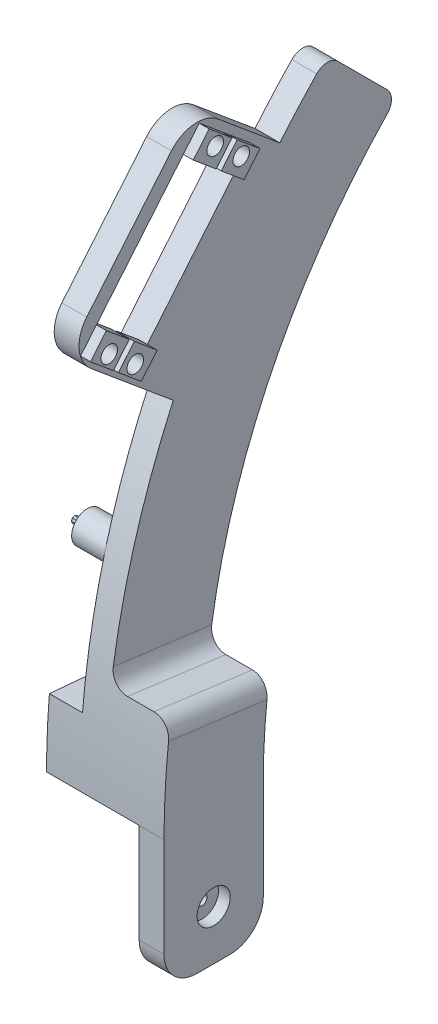
SolidWorks part; units mm, degrees
ref_plane "Front Plane" through (0, 0, 0) normal (0, 0, 1) x (1, 0, 0)
ref_plane "Top Plane" through (0, 0, 0) normal (0, 1, 0) x (1, 0, 0)
ref_plane "Right Plane" through (0, 0, 0) normal (1, 0, 0) x (0, 0, -1)
sketch "Sketch2" plane through (0, 0, 0) normal (1, 0, 0) x (0, 0, -1)
  line L0 (-197.177, 0) -> (-167.177, 0)
  line L1 (-129.8116, 162.6346) -> (-108.5984, 141.4214)
  arc A0 (-167.177, 0) -> (-108.5984, 141.4214) centre (32.823, 0) cw
  arc A1 (-197.177, 0) -> (-129.8116, 162.6346) centre (32.823, 0) cw
  dimension "D4" = 200
  dimension "D1" = 30
  dimension "D2" = 30
  dimension "D3" = 45
extrude "Curve Main Body" add sketch "Sketch2" along normal blind 35.5
sketch "Sketch6" plane through (35.5, 0, 0) normal (1, 0, 0) x (0, 0, -1)
  line L0 (-165.466, 26.1052) -> (-195.2093, 30.021)
  line L1 (-108.5984, 141.4214) -> (-129.8116, 162.6346)
  line L2 (-197.177, 0) -> (-167.177, 0) construction
  arc A0 (-108.5984, 141.4214) -> (-167.177, 0) centre (32.823, 0) ccw construction
  arc A1 (-129.8116, 162.6346) -> (-197.177, 0) centre (32.823, 0) ccw construction
  arc A2 (-165.466, 26.1052) -> (-108.5984, 141.4214) centre (32.823, 0) cw
  arc A3 (-129.8116, 162.6346) -> (-195.2093, 30.021) centre (32.823, 0) ccw
  dimension "D1" = 30
  dimension "D2" = 7.5
extrude "Cut-Extrude2" cut sketch "Sketch6" against normal offset from surface (18 mm away) 17.5 up to face at (0, 79.1455, 158.2511)
sketch "Sketch7" plane through (0, 0, 0) normal (-1, 0, 0) x (0, 0, 1)
  line L0 (166.416, 17.4311) -> (196.3018, 20.0458)
  line L1 (167.177, 0) -> (197.177, 0) construction
  line L3 (129.8116, 162.6346) -> (108.5984, 141.4214)
  arc A0 (167.177, 0) -> (108.5984, 141.4214) centre (-32.823, 0) ccw construction
  arc A1 (197.177, 0) -> (129.8116, 162.6346) centre (-32.823, 0) ccw construction
  arc A2 (196.3018, 20.0458) -> (129.8116, 162.6346) centre (-32.823, 0) ccw
  arc A3 (108.5984, 141.4214) -> (166.416, 17.4311) centre (-32.823, 0) cw
  dimension "D1" = 30
  dimension "D2" = 5
extrude "Cut-Extrude3" cut sketch "Sketch7" against normal offset from surface (10 mm away) 7.5 up to face at (17.5, 92.5688, 154.888)
fillet "Fillet3" radius 5 2 edges at (35.5, 28.0631, 180.3377) (17.5, 28.0631, 180.3377)
mirror "Mirror3" about plane through (0, 0, -32.823) normal (-1, 0, 0) of "Curve Main Body", "Cut-Extrude2", "Cut-Extrude3", "Fillet3"
sketch "Sketch14" plane through (0, 0, 0) normal (0, -1, 0) x (1, 0, 0)
  line L0 (35.5, 167.177) -> (-35.5, 167.177) construction
  line L1 (-35.5, 197.177) -> (-28, 197.177)
  line L2 (-35.5, 197.177) -> (-35.5, 167.177)
  line L3 (-35.5, 167.177) -> (-28, 167.177)
  line L4 (-28, 197.177) -> (-28, 167.177)
  line L5 (0, 197.177) -> (0, 167.177) construction
  line L6 (35.5, 197.177) -> (-35.5, 197.177) construction
  line L7 (28, 197.177) -> (28, 167.177)
  line L8 (35.5, 167.177) -> (28, 167.177)
  line L9 (35.5, 197.177) -> (35.5, 167.177)
  line L10 (35.5, 197.177) -> (28, 197.177)
  dimension "D1" = 7.5
extrude "Boss-Extrude9" add sketch "Sketch14" along normal blind 40
sketch "Sketch17" plane through (-10, 0, 0) normal (1, 0, 0) x (0, 0, -1)
  line L0 (-108.5984, 141.4214) -> (-129.8116, 162.6346) construction
  line L2 (-115.2769, 141.3824) -> (-191.7402, 49.7129) construction
  line L3 (-196.3018, 20.0458) -> (-154.4398, 70.2329) construction
  arc A0 (-108.5984, 141.4214) -> (-166.416, 17.4311) centre (32.823, 0) ccw construction
  circle A1 centre (-115.2769, 141.3824) radius 4.75
  circle A4 centre (-184.8336, 57.9931) radius 4.75
  arc A5 (-129.8116, 162.6346) -> (-196.3018, 20.0458) centre (32.823, 0) ccw construction
  dimension "D3" = 9.5
  dimension "D2" = 15.5
extrude "Boss-Extrude6" add sketch "Sketch17" along normal up to surface (20 mm away) up to face at (10, 88.1231, 156.1576)
sketch "Sketch18" plane through (-10, 0, 0) normal (1, 0, 0) x (0, 0, -1)
  line L0 (-184.8336, 57.9931) -> (-115.2769, 141.3824) construction
  line L1 (-150.0552, 99.6877) -> (-167.0261, 113.8435) construction
  line L2 (-208.9415, 122.7617) -> (-162.8661, 84.3292)
  line L3 (-208.9415, 122.7617) -> (-170.5091, 168.8371)
  line L4 (-162.8661, 84.3292) -> (-124.4336, 130.4047)
  line L5 (-170.5091, 168.8371) -> (-124.4336, 130.4047)
  arc A0 (-129.8116, 162.6346) -> (-189.4234, 59.216) centre (32.823, 0) ccw construction
  circle A1 centre (-184.8336, 57.9931) radius 4.75 construction
  point P10 (-173.093, 118.9039)
  dimension "D1" = 60
  dimension "D2" = 20
  dimension "D3" = 60
extrude "Servo Placement Body" add sketch "Sketch18" against normal up to surface (7.5 mm away) up to face at (-17.5, 94.9241, 154.1509)
sketch "Sketch26" plane through (-10, 0, 0) normal (1, 0, 0) x (0, 0, -1)
  line L0 (-144.1759, 146.8721) -> (-170.5091, 168.8371)
  line L1 (-170.5091, 168.8371) -> (-208.9415, 122.7617)
  line L2 (-208.9415, 122.7617) -> (-176.3704, 95.5935)
  line L3 (-144.1759, 146.8721) -> (-176.3704, 95.5935)
extrude "Boss-Extrude10" add sketch "Sketch26" along normal up to surface (27.5 mm away) up to face at (17.5, 94.9241, 154.1509)
sketch "Sketch29" plane through (0, 153.1437, 183.5993) normal (0, 0.6405, 0.7679) x (1, 0, 0)
  line L1 (10, 20.4362) -> (-10, 20.4362)
  line L2 (10, 20.4362) -> (10, -39.5638)
  line L3 (10, -39.5638) -> (-10, -39.5638)
  line L4 (-10, 20.4362) -> (-10, -39.5638)
extrude "Cut-Extrude8" cut sketch "Sketch29" against normal through all both
sketch "Sketch21" plane through (0, 0, 0) normal (1, 0, 0) x (0, 0, -1)
  line L1 (-209.5581, 171.1954) -> (-104.3811, 171.1954)
  line L2 (-209.5581, 171.1954) -> (-209.5581, -48.5736)
  line L3 (-209.5581, -48.5736) -> (-104.3811, -48.5736)
  line L4 (-104.3811, 171.1954) -> (-104.3811, -48.5736)
extrude "Make Half" cut sketch "Sketch21" against normal through all
chamfer "Chamfer2" distance 30 distance2 19 1 edges at (14, 0, 167.177) first distance on face at (14, 0, 182.177)
sketch "Sketch35" plane through (17.5, 0, 0) normal (1, 0, 0) x (0, 0, -1)
  line L0 (-184.8336, 57.9931) -> (-115.2769, 141.3824) construction
  line L1 (-150.0552, 99.6877) -> (-196.1307, 138.1202) construction
  line L2 (-208.9415, 122.7617) -> (-170.5091, 168.8371) construction
  line L3 (-204.3969, 121.1847) -> (-189.0384, 108.3739)
  line L4 (-204.3969, 121.1847) -> (-168.5267, 164.1885)
  line L5 (-189.0384, 108.3739) -> (-153.1682, 151.3777)
  line L6 (-168.5267, 164.1885) -> (-153.1682, 151.3777)
  line L7 (-176.3704, 95.5935) -> (-208.9415, 122.7617) construction
  line L8 (-196.7177, 114.7793) -> (-160.8474, 157.7831) construction
  dimension "D1" = 56
  dimension "D2" = 20
  dimension "D3" = 45.5
  dimension "D4" = 18.3
sketch "Sketch30" plane through (28, 0, 0) normal (-1, 0, 0) x (0, 0, 1)
  line L0 (197.177, 0) -> (167.177, 0) construction
  line L1 (182.177, 0) -> (182.177, -40) construction
  line L2 (197.177, -40) -> (167.177, -40) construction
  circle A0 centre (182.177, -25) radius 4.5
  dimension "D2" = 9
  dimension "D1" = 25
sketch "Sketch31" plane through (0, 0, 0) normal (-1, 0, 0) x (0, 0, 1)
  line L0 (115.2769, 146.1324) -> (115.2769, 136.6324) construction
  line L1 (116.2769, 141.3824) -> (115.984, 142.0895)
  line L2 (115.2769, 142.3824) -> (114.5698, 142.0895)
  line L3 (114.5698, 142.0895) -> (114.2769, 141.3824)
  line L4 (114.2769, 141.3824) -> (114.5698, 140.6753)
  line L5 (114.5698, 140.6753) -> (115.2769, 140.3824)
  line L6 (115.2769, 140.3824) -> (115.984, 140.6753)
  line L7 (115.984, 140.6753) -> (116.2769, 141.3824)
  line L8 (115.984, 142.0895) -> (115.2769, 142.3824)
  line L9 (184.8336, 62.7431) -> (184.8336, 53.2431) construction
  line L11 (184.8336, 58.9931) -> (184.1264, 58.7002)
  line L12 (184.1264, 58.7002) -> (183.8336, 57.9931)
  line L13 (183.8336, 57.9931) -> (184.1264, 57.286)
  line L14 (184.1264, 57.286) -> (184.8336, 56.9931)
  line L15 (184.8336, 56.9931) -> (185.5407, 57.286)
  line L16 (185.5407, 57.286) -> (185.8336, 57.9931)
  line L17 (185.8336, 57.9931) -> (185.5407, 58.7002)
  line L18 (185.5407, 58.7002) -> (184.8336, 58.9931)
  arc A0 (111.8412, 138.1025) -> (111.9182, 144.7411) centre (115.2769, 141.3824) ccw construction
  circle A1 centre (115.2769, 141.3824) radius 4.75 construction
  circle A2 centre (115.2769, 141.3824) radius 1 construction
  circle A3 centre (184.8336, 57.9931) radius 4.75 construction
  circle A4 centre (184.8336, 57.9931) radius 1 construction
  dimension "D1" = 2
extrude "Male Jack" add sketch "Sketch31" along normal blind 4
chamfer "Male Jack Chamfer" distance 0.2 16 edges at (-4, 140.5288, 114.9234) (-4, 141.0288, 114.4234) (-4, 140.5288, 115.6305) (-4, 141.0288, 116.1305) (-4, 141.7359, 116.1305) (-4, 142.2359, 115.6305) (-4, 142.2359, 114.9234) (-4, 141.7359, 114.4234) (-4, 57.1395, 185.1871) (-4, 57.6395, 185.6871) (-4, 58.3466, 185.6871) (-4, 58.8466, 185.1871) (-4, 58.8466, 184.48) (-4, 58.3466, 183.98) (-4, 57.6395, 183.98) (-4, 57.1395, 184.48)
extrude "Servo Placement" add sketch "Sketch35" along normal blind 3
sketch "Sketch36" plane through (20.5, 0, 0) normal (1, 0, 0) x (0, 0, -1)
  line L0 (-196.7177, 114.7793) -> (-160.8474, 157.7831) construction
  line L1 (-204.3969, 121.1847) -> (-189.0384, 108.3739) construction
  line L4 (-184.2344, 114.1333) -> (-157.9722, 145.6182)
  line L5 (-199.5929, 126.9441) -> (-173.3307, 158.429)
  line L7 (-184.2344, 114.1333) -> (-173.3307, 158.429) construction
  line L8 (-199.5929, 126.9441) -> (-157.9722, 145.6182) construction
  line L13 (-186.4618, 142.6866) -> (-171.1033, 129.8758) construction
  line L15 (-173.3307, 158.429) -> (-157.9722, 145.6182) construction
  line L16 (-199.5929, 126.9441) -> (-184.2344, 114.1333) construction
  line L17 (-173.3307, 158.429) -> (-166.4194, 152.6642)
  line L18 (-166.4194, 152.6642) -> (-161.6154, 158.4236)
  line L19 (-161.6154, 158.4236) -> (-160.0795, 157.1425)
  line L20 (-157.9722, 145.6182) -> (-164.8836, 151.3831)
  line L21 (-164.8836, 151.3831) -> (-160.0795, 157.1425)
  line L22 (-184.2344, 114.1333) -> (-191.1457, 119.8982)
  line L23 (-191.1457, 119.8982) -> (-195.9498, 114.1388)
  line L24 (-197.4856, 115.4198) -> (-195.9498, 114.1388)
  line L25 (-192.6816, 121.1793) -> (-197.4856, 115.4198)
  line L26 (-199.5929, 126.9441) -> (-192.6816, 121.1793)
  line L27 (-153.1682, 151.3777) -> (-168.5267, 164.1885) construction
  line L28 (-189.0384, 108.3739) -> (-153.1682, 151.3777) construction
  line L29 (-168.5267, 164.1885) -> (-204.3969, 121.1847) construction
  line L31 (-153.1682, 151.3777) -> (-168.5267, 164.1885) construction
  line L32 (-189.0384, 108.3739) -> (-153.1682, 151.3777) construction
  circle A0 centre (-166.7008, 158.7589) radius 2.5
  circle A1 centre (-158.8373, 152.1997) radius 2.5
  circle A2 centre (-190.8643, 113.8035) radius 2.5
  circle A3 centre (-198.7278, 120.3626) radius 2.5
  point P7 (-178.7826, 136.2812)
  dimension "D4" = 5
  dimension "D1" = 2
  dimension "D2" = 4.88
  dimension "D3" = 3
  dimension "D5" = 7.5
extrude "Servo Hole" cut sketch "Sketch36" against normal through all
sketch "Sketch37" plane through (10, 0, 0) normal (-1, 0, 0) x (0, 0, 1)
  line L0 (160.8474, 157.7831) -> (196.7177, 114.7793) construction
  line L3 (153.1682, 151.3777) -> (168.5267, 164.1885)
  line L4 (153.1682, 151.3777) -> (189.0384, 108.3739)
  line L5 (168.5267, 164.1885) -> (204.3969, 121.1847)
  line L6 (189.0384, 108.3739) -> (204.3969, 121.1847)
  line L7 (153.1682, 151.3777) -> (204.3969, 121.1847) construction
  line L8 (168.5267, 164.1885) -> (189.0384, 108.3739) construction
  line L11 (199.5929, 126.9441) -> (173.3307, 158.429) construction
  line L12 (157.9722, 145.6182) -> (184.2344, 114.1333) construction
  line L13 (161.6154, 158.4236) -> (160.0795, 157.1425) construction
  line L14 (195.9498, 114.1388) -> (197.4856, 115.4198) construction
  point P7 (178.7826, 136.2812)
extrude "Servo Placement Completion" cut sketch "Sketch37" against normal offset from surface (5 mm away) 2.5 up to face at (17.5, 113.6743, 163.5869)
fillet "Biceps Connection Fillet" radius 10 2 edges at (31.75, -40, 167.177) (31.75, -40, 197.177)
fillet "Bow Connection Fillet" radius 4.5 2 edges at (13.75, 162.6346, 129.8116) (13.75, 141.4214, 108.5984)
fillet "Servo Hole Fillet" radius 10 2 edges at (13.75, 168.8371, 170.5091) (13.75, 122.7617, 208.9415)
extrude "Forearm Servo Connection Outer" cut sketch "Sketch30" against normal blind 2
sketch "Sketch34" plane through (30, 0, 0) normal (-1, 0, 0) x (0, 0, 1)
  circle A0 centre (182.177, -25) radius 1.5
  circle A1 centre (182.177, -25) radius 4.5 construction
  dimension "D1" = 3
extrude "Forearm Servo Connection Inner" cut sketch "Sketch34" against normal up to surface (5.5 mm away) up to face at (35.5, -12.239, 181.9436)
sketch "Sketch38" plane through (35.5, 0, 0) normal (1, 0, 0) x (0, 0, -1)
  circle A0 centre (-182.177, -25) radius 5
  dimension "D1" = 10
extrude "Cut-Extrude14" cut sketch "Sketch38" against normal offset from surface (3.5 mm away) 2 up to face at (30, -25, 183.677)
sketch "Sketch39" plane through (0, 0, 0) normal (-1, 0, 0) x (0, 0, 1)
  line L0 (182.177, -25) -> (182.6483, 9.2015) construction
  line L1 (169.2611, 17.6801) -> (197.177, 0) construction
  line L2 (182.6483, 9.2015) -> (182.7815, 18.8629) construction
  line L3 (169.2611, 17.6801) -> (196.3018, 20.0458) construction
  line L4 (183.7148, 14.0184) -> (183.4317, 14.7295)
  line L5 (182.7287, 15.0321) -> (182.0176, 14.749)
  line L6 (182.0176, 14.749) -> (181.715, 14.046)
  line L7 (181.715, 14.046) -> (181.9981, 13.3349)
  line L8 (181.9981, 13.3349) -> (182.7011, 13.0323)
  line L9 (182.7011, 13.0323) -> (183.4122, 13.3154)
  line L10 (183.4122, 13.3154) -> (183.7148, 14.0184)
  line L11 (183.4317, 14.7295) -> (182.7287, 15.0321)
  circle A0 centre (182.7149, 14.0322) radius 1 construction
  dimension "D1" = 2
extrude "Cut-Extrude15" cut sketch "Sketch39" against normal blind 5
